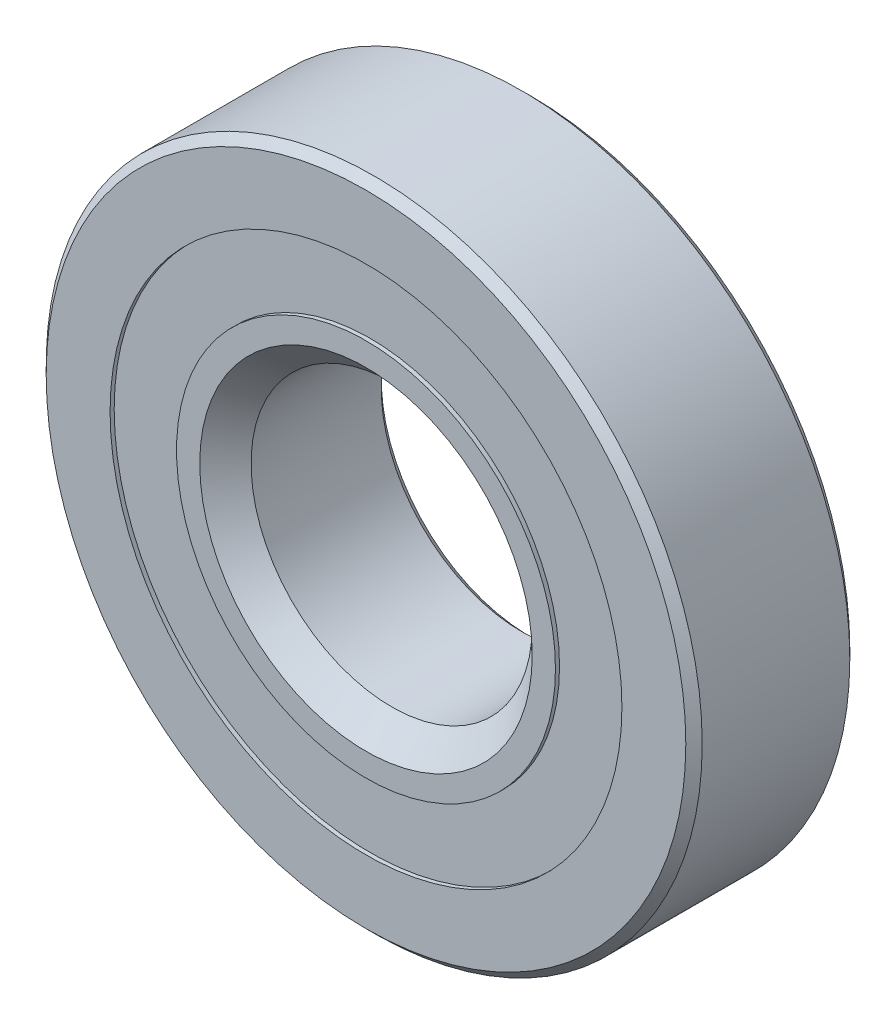
SolidWorks part; units mm, degrees
ref_plane "Front Plane" through (0, 0, 0) normal (0, 0, 1) x (1, 0, 0)
ref_plane "Top Plane" through (0, 0, 0) normal (0, 1, 0) x (1, 0, 0)
ref_plane "Right Plane" through (0, 0, 0) normal (1, 0, 0) x (0, 0, -1)
sketch "Sketch1" plane through (0, 0, 0) normal (1, 0, 0) x (0, 0, -1)
  line L0 (-2.7781, 0) -> (2.7781, 0) construction
  line L1 (0, 11.1125) -> (0, -11.1125) construction
  line L2 (2.5003, 11.1125) -> (-2.5003, 11.1125)
  line L3 (-2.5003, 11.1125) -> (-2.7781, 10.8347)
  line L4 (-2.7781, 10.8347) -> (-2.7781, 8.6702)
  line L5 (-2.7781, 8.6702) -> (-1.2347, 8.6702)
  line L6 (2.7781, 8.6702) -> (1.2347, 8.6702)
  line L7 (2.7781, 10.8347) -> (2.7781, 8.6702)
  line L8 (2.5003, 11.1125) -> (2.7781, 10.8347)
  line L9 (0, 11.1125) -> (0, 7.9375) construction
  line L10 (0, 7.9375) -> (0, 4.7625) construction
  arc A0 (-1.2347, 8.6702) -> (1.2347, 8.6702) centre (0, 7.9375) cw
  point P14 (0, 4.7625)
  dimension "D3" = 2.4694
  dimension "D1" = 45
  dimension "Width" = 5.5562
  dimension "OD" = 22.225
  dimension "D2" = 0.2778
  dimension "Shaft Dia" = 9.525
  dimension "D4" = 0.7327
revolve "Revolve1" add sketch "Sketch1" angle 360 about L0
sketch "Sketch2" plane through (0, 0, 0) normal (1, 0, 0) x (0, 0, -1)
  line L0 (-2.6392, 7.2048) -> (-1.2347, 7.2048)
  line L1 (-2.7781, 10.8347) -> (-2.7781, -10.8347) construction
  line L2 (-2.7781, 6.4185) -> (-2.6392, 6.4185) construction
  line L3 (-2.6392, 6.2796) -> (-1.9918, 5.6321)
  line L4 (-1.9918, 5.6321) -> (0, 5.6321)
  line L5 (0, 11.1125) -> (0, -11.1125) construction
  line L6 (0, 5.6321) -> (0, 6.5018)
  line L7 (0, 6.5018) -> (0, 4.7625) construction
  line L8 (-2.7781, 7.2048) -> (-2.7781, 5.6321) construction
  line L9 (-2.7781, 5.6321) -> (-1.9918, 5.6321) construction
  line L10 (-2.6392, 7.2048) -> (-2.6392, 6.2796)
  line L11 (-2.6392, 7.2048) -> (-2.6392, 10.9736) construction
  line L12 (-2.5003, 11.1125) -> (-2.7781, 10.8347) construction
  arc A0 (-1.2347, 7.2048) -> (0, 6.5018) centre (0, 7.9375) ccw
  arc A1 (1.2347, 8.6702) -> (-1.2347, 8.6702) centre (0, 7.9375) ccw construction
  circle A2 centre (0, 7.9375) radius 1.4357 construction
  dimension "D1" = 45
revolve "Revolve2" [suppressed] add sketch "Sketch2" angle 360 about L0
sketch "Sketch3" plane through (0, 0, 0) normal (1, 0, 0) x (0, 0, -1)
  line L0 (-2.6392, 6.2796) -> (-1.9918, 5.6321)
  line L1 (-1.9918, 5.6321) -> (0, 5.6321)
  line L2 (0, 5.6321) -> (0, 6.5018)
  line L3 (-2.7781, 6.4185) -> (-2.7781, 5.6321)
  line L4 (-2.7781, 7.2048) -> (-2.7781, 5.6321) construction
  line L5 (-2.7781, 5.6321) -> (-1.9085, 4.7625)
  line L6 (-1.9085, 4.7625) -> (2.5003, 4.7625)
  line L7 (2.5003, 11.1125) -> (2.5003, -11.1125) construction
  line L8 (2.5003, 4.7625) -> (2.7781, 5.0403)
  line L9 (2.7781, -10.8347) -> (2.7781, 10.8347) construction
  line L10 (2.7781, 5.0403) -> (2.7781, 7.2048)
  line L11 (2.7781, 7.2048) -> (1.2347, 7.2048)
  line L12 (-2.7781, 6.4185) -> (-2.6392, 6.4185)
  line L13 (2.5003, 11.1125) -> (2.7781, 10.8347) construction
  line L14 (-2.6392, 6.4185) -> (-2.6392, 6.2796)
  circle A0 centre (0, 7.9375) radius 1.4357 construction
  arc A1 (1.2347, 7.2048) -> (0, 6.5018) centre (0, 7.9375) cw
revolve "Revolve3" add sketch "Sketch3" angle 360 about L0
sketch "Sketch4" plane through (0, 0, 0) normal (1, 0, 0) x (0, 0, -1)
  line L0 (-1.4357, 7.9375) -> (1.4357, 7.9375)
  circle A1 centre (0, 7.9375) radius 1.4357 construction
  arc A2 (-1.4357, 7.9375) -> (1.4357, 7.9375) centre (0, 7.9375) cw
  arc A3 (1.2347, 8.6702) -> (-1.2347, 8.6702) centre (0, 7.9375) ccw construction
revolve "Revolve4" add sketch "Sketch4" angle 360 about L0
ref_axis "Axis1" through (0, 0, -2.7781) along (0, 0, 1)
pattern_circular "CirPattern1" count 12 every 30 about axis through (0, 0, -2.7781) along (0, 0, 1) of bodies 104
sketch "Sketch5" plane through (0, 0, 0) normal (1, 0, 0) x (0, 0, -1)
  line L0 (-2.7781, 8.6702) -> (-1.2347, 8.6702) construction
  line L1 (-2.6392, 8.6702) -> (-1.4357, 8.6702)
  line L2 (-2.6392, 8.6702) -> (-2.6392, 6.4185)
  line L3 (-2.6392, 6.4185) -> (-1.4357, 6.4185)
  line L4 (-1.4357, 8.6702) -> (-1.4357, 6.4185)
  line L6 (-2.5003, 11.1125) -> (-2.7781, 10.8347) construction
  line L7 (0, 11.1125) -> (0, 4.7625) construction
  line L8 (2.6392, 6.4185) -> (1.4357, 6.4185)
  line L9 (1.4357, 8.6702) -> (1.4357, 6.4185)
  line L10 (2.6392, 8.6702) -> (1.4357, 8.6702)
  line L11 (2.6392, 8.6702) -> (2.6392, 6.4185)
  circle A0 centre (0, 7.9375) radius 1.4357 construction
  point P10 (-2.6392, 10.9736)
revolve "Revolve5" add sketch "Sketch5" angle 360 about L0
equation "\"D2@Sketch1\" = \"Width@Sketch1\"*.05"
equation "\"D3@Sketch1\" = \"Width@Sketch1\"/2.25"
equation "\"D4@Sketch1\" = (((\"OD@Sketch1\"-\"Width@Sketch1\")/2)/3.25)/3.5"
equation "\"D2@CirPattern1\" = 360/\"Balls@CirPattern1\""
